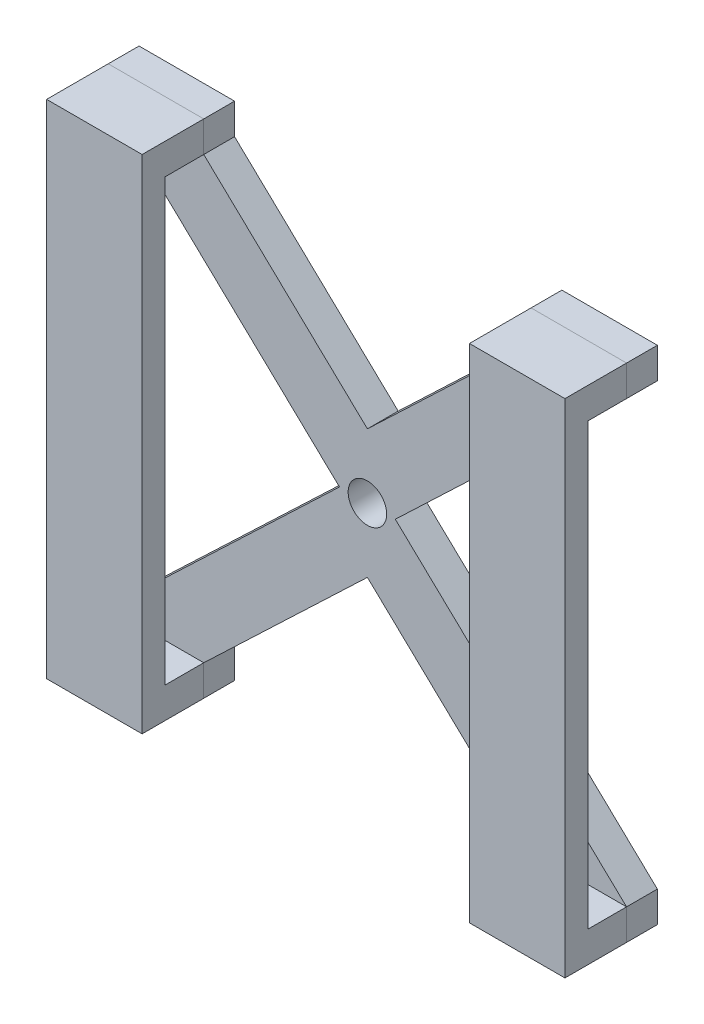
SolidWorks part; units mm, degrees
other "Element opisowy1"
other "Element opisowy2"
other "Element opisowy3"
other "Element opisowy4"
other "Folder spoin"
other "Ścieg spoiny1"
other "Ścieg spoiny2"
other "Ścieg spoiny3"
other "Ścieg spoiny4"
ref_plane "Płaszczyzna przednia" through (0, 0, 0) normal (0, 0, 1) x (1, 0, 0)
ref_plane "Płaszczyzna górna" through (0, 0, 0) normal (0, 1, 0) x (1, 0, 0)
ref_plane "Płaszczyzna prawa" through (0, 0, 0) normal (1, 0, 0) x (0, 0, -1)
sketch "Szkic1" plane through (0, 0, 0) normal (0, 0, 1) x (1, 0, 0)
  line L0 (0, 17.8465) -> (0, -34.5488) construction
  line L7 (-45.4305, 0) -> (52.6784, 0) construction
  line L8 (21.25, -28.575) -> (0, -8.3511)
  line L9 (27.7305, -22.9424) -> (3.624, 0)
  line L10 (-21.25, -28.575) -> (-21.25, -32.575)
  line L11 (27.7305, -22.9424) -> (33.6489, -28.575)
  line L12 (21.25, -28.575) -> (21.25, -32.575)
  line L13 (21.25, -32.575) -> (33.6489, -32.575)
  line L14 (33.6489, -32.575) -> (33.6489, -28.575)
  line L15 (-21.25, -32.575) -> (-33.6489, -32.575)
  line L16 (-33.6489, -32.575) -> (-33.6489, -28.575)
  line L17 (-27.7305, -22.9424) -> (-33.6489, -28.575)
  line L18 (-21.25, -28.575) -> (0, -8.3511)
  line L19 (-27.7305, -22.9424) -> (-3.624, 0)
  line L20 (-27.7305, 22.9424) -> (-33.6489, 28.575)
  line L21 (-33.6489, 32.575) -> (-33.6489, 28.575)
  line L22 (-21.25, 32.575) -> (-33.6489, 32.575)
  line L23 (-27.7305, 22.9424) -> (-3.624, 0)
  line L24 (-21.25, 28.575) -> (0, 8.3511)
  line L25 (21.25, 28.575) -> (0, 8.3511)
  line L26 (27.7305, 22.9424) -> (3.624, 0)
  line L27 (33.6489, 32.575) -> (33.6489, 28.575)
  line L28 (21.25, 32.575) -> (33.6489, 32.575)
  line L29 (21.25, 28.575) -> (21.25, 32.575)
  line L30 (27.7305, 22.9424) -> (33.6489, 28.575)
  line L31 (-21.25, 28.575) -> (-21.25, 32.575)
  point P0 (0, 0)
  dimension "D1" = 57.15
  dimension "D2" = 42.5
  dimension "D3" = 8.5478
  dimension "D4" = 4
  dimension "D5" = 12.3989
extrude "Dodanie-wyciągnięcie1" add sketch "Szkic1" along normal blind 4
sketch "Szkic2" plane through (0, 0, 4) normal (0, 0, 1) x (1, 0, 0)
  line L1 (-33.6489, 32.575) -> (-21.25, 32.575)
  line L2 (-33.6489, 32.575) -> (-33.6489, 28.575)
  line L3 (-33.6489, 28.575) -> (-21.25, 28.575)
  line L4 (-21.25, 32.575) -> (-21.25, 28.575)
  line L5 (21.25, 32.575) -> (33.6489, 32.575)
  line L6 (21.25, 32.575) -> (21.25, 28.575)
  line L7 (21.25, 28.575) -> (33.6489, 28.575)
  line L8 (33.6489, 32.575) -> (33.6489, 28.575)
  line L9 (33.6489, -32.575) -> (21.25, -32.575)
  line L10 (33.6489, -32.575) -> (33.6489, -28.575)
  line L11 (33.6489, -28.575) -> (21.25, -28.575)
  line L12 (21.25, -32.575) -> (21.25, -28.575)
  line L13 (-21.25, -32.575) -> (-33.6489, -32.575)
  line L14 (-21.25, -32.575) -> (-21.25, -28.575)
  line L15 (-21.25, -28.575) -> (-33.6489, -28.575)
  line L16 (-33.6489, -32.575) -> (-33.6489, -28.575)
extrude "Dodanie-wyciągnięcie2" add sketch "Szkic2" along normal blind 8
sketch "Szkic3" plane through (0, 0, 12) normal (0, 0, 1) x (1, 0, 0)
  line L1 (-33.6489, 32.575) -> (-21.25, 32.575)
  line L2 (-33.6489, 32.575) -> (-33.6489, -32.575)
  line L3 (-33.6489, -32.575) -> (-21.25, -32.575)
  line L4 (-21.25, 32.575) -> (-21.25, -32.575)
  line L5 (33.6489, -32.575) -> (21.25, -32.575)
  line L6 (33.6489, -32.575) -> (33.6489, 32.575)
  line L7 (33.6489, 32.575) -> (21.25, 32.575)
  line L8 (21.25, -32.575) -> (21.25, 32.575)
extrude "Dodanie-wyciągnięcie3" add sketch "Szkic3" against normal blind 3
split "Podziel1" bodies to split 103 resulting bodies 104 105 106 split by face at (0, 0, 4)
sketch "Szkic4" plane through (0, 0, 0) normal (0, 0, -1) x (-1, 0, 0)
  circle A0 centre (0, 0) radius 2.5
  dimension "D1" = 5
extrude "Wytnij-wyciągnięcie1" cut sketch "Szkic4" against normal blind 10
